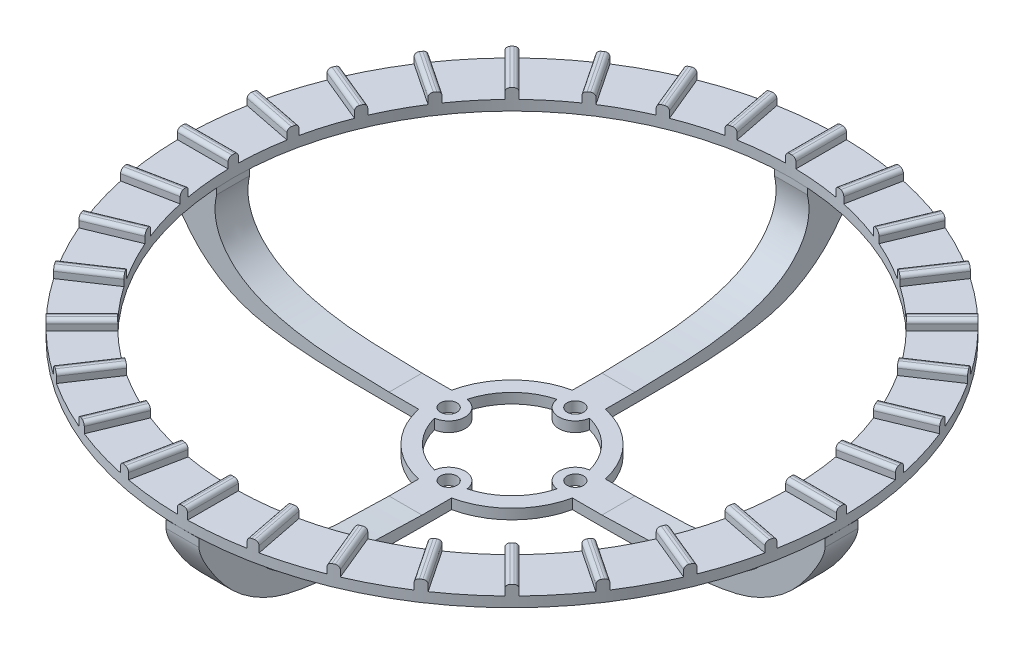
SolidWorks part; units mm, degrees
ref_plane "Front Plane" through (0, 0, 0) normal (0, 0, 1) x (1, 0, 0)
ref_plane "Top Plane" through (0, 0, 0) normal (0, 1, 0) x (1, 0, 0)
ref_plane "Right Plane" through (0, 0, 0) normal (1, 0, 0) x (0, 0, -1)
sketch "Sketch1" plane through (0, 0, 0) normal (0, 1, 0) x (1, 0, 0)
  circle A0 centre (0, 0) radius 55
  circle A1 centre (0, 0) radius 65
  dimension "D2" = 65
  dimension "D1" = 10
extrude "Boss-Extrude1" add sketch "Sketch1" along normal blind 2
sketch "Sketch2" plane through (0, 2, 0) normal (0, 1, 0) x (1, 0, 0)
  line L0 (0, 0) -> (0, 65) construction
  line L1 (-1, 64.9923) -> (-1, 54.9909)
  line L2 (1, 64.9923) -> (1, 54.9909)
  line L3 (-1, 59.9916) -> (1, 59.9916) construction
  circle A0 centre (0, 0) radius 65 construction
  circle A1 centre (0, 0) radius 55 construction
  arc A2 (-1, 64.9923) -> (1, 64.9923) centre (0, 0) cw
  arc A3 (-1, 54.9909) -> (1, 54.9909) centre (0, 0) cw
  point P17 (0, 59.9916)
  dimension "D1" = 2
extrude "Boss-Extrude3" add sketch "Sketch2" along normal blind 2
fillet "Fillet1" radius 0.75 2 edges at (1, 4, -59.9916) (-1, 4, -59.9916)
pattern_circular "CirPattern1" count 32 over 360 about axis through (0, 0, 0) along (0, 1, 0) of "Boss-Extrude3", "Fillet1"
ref_plane "Plane1" through (0, -18, 0) normal (0, 1, 0) x (1, 0, 0)
sketch "Sketch4" plane through (0, -18, 0) normal (0, 1, 0) x (1, 0, 0)
  line L0 (0, 0) -> (-12.5, 0) construction
  circle A1 centre (-12.5, 0) radius 1.625
  circle A2 centre (-12.5, 0) radius 3.25
  dimension "D1" = 3.25
  dimension "D2" = 6.5
  dimension "D3" = 12.5
extrude "Boss-Extrude4" add sketch "Sketch4" against normal blind 2 separate body
pattern_circular "CirPattern9" count 4 over 360 about axis through (0, 2, 0) along (0, -1, 0) reverse direction yes of bodies 105
sketch "Sketch5" plane through (0, 0, 0) normal (0, 0, 1) x (1, 0, 0)
  line L0 (-12.0842, -18) -> (-21.0009, -18)
  line L1 (-9.25, -18) -> (-15.75, -18) construction
  line L2 (-12.0842, -18) -> (-12.0842, -20)
  line L3 (-15.75, -20) -> (-9.25, -20) construction
  line L4 (-12.0842, -20) -> (-21.0009, -20)
  line L5 (-65, 0) -> (-65, -1.525)
  line L6 (-65, 0) -> (-55, 0)
  line L7 (-55, 0) -> (-55, -1.2726)
  spline S0 degree 3 poles (-65, -1.525) (-64.9467, -2.9281) (-60.7658, -10.5421) (-53.1698, -16.7265) (-45.2571, -19.0784) (-33.6054, -20.068) (-21.0009, -20) knots 0 0 0 0 0.088914 0.316963 0.647006 1 1 1 1
  spline S1 degree 3 poles (-55, -1.2726) (-56.2993, -6.3598) (-52.2867, -12.6584) (-38.696, -17.9624) (-28.5366, -17.7806) (-21.0009, -18) knots 0 0 0 0 0.305757 0.470347 1 1 1 1
  point P15 (-65, -1.525)
  point P17 (-55, -1.2726)
  point P21 (-63.5265, -7.401)
  point P23 (-54.6519, -15.1014)
  point P25 (-62.6372, -6.8391)
  point P27 (-44.121, -18.8385)
  point P28 (-35.7655, -19.7046)
  dimension "D1" = 51.8984
extrude "Boss-Extrude5" add sketch "Sketch5" along normal blind 3.25 and the other way blind 3.25
pattern_circular "CirPattern7" count 4 over 360 about axis through (0, 2, 0) along (0, -1, 0) of "Boss-Extrude5" reverse direction yes
combine bodies "Combine1" operation type add bodies to combine 111 110 109 108
sketch "Sketch7" plane through (0, -18, 0) normal (0, 1, 0) x (1, 0, 0)
  circle A0 centre (0, 0) radius 12.5
  circle A1 centre (0, 0) radius 15.5
  dimension "D1" = 31
  dimension "D2" = 25
extrude "Boss-Extrude6" add sketch "Sketch7" against normal up to surface (2 mm away) up to face at (-11.4796, -20, 0)
sketch "Sketch6" plane through (0, -18, 0) normal (0, 1, 0) x (1, 0, 0)
  circle A0 centre (-12.5, 0) radius 1.625
  circle A1 centre (0, 12.5) radius 1.625
  circle A2 centre (12.5, 0) radius 1.625
  circle A3 centre (0, -12.5) radius 1.625
extrude "Cut-Extrude2" cut sketch "Sketch6" against normal blind 4
